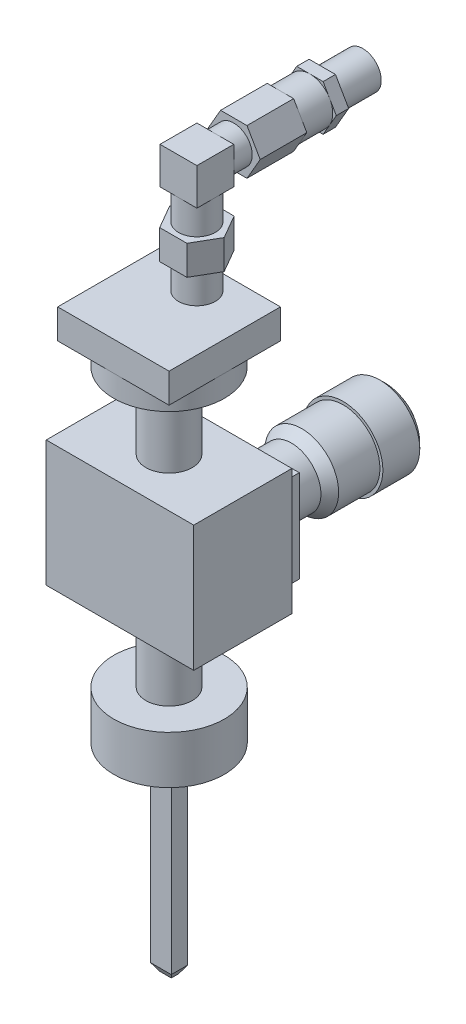
SolidWorks part; units mm, degrees
ref_plane "Front Plane" through (0, 0, 0) normal (0, 0, 1) x (1, 0, 0)
ref_plane "Top Plane" through (0, 0, 0) normal (0, 1, 0) x (1, 0, 0)
ref_plane "Right Plane" through (0, 0, 0) normal (1, 0, 0) x (0, 0, -1)
sketch "Sketch1" plane through (0, 0, 0) normal (0, 1, 0) x (1, 0, 0)
  line L1 (0, 0) -> (3.556, 0)
  line L2 (0, 0) -> (0, -2.794)
  line L3 (0, -2.794) -> (3.556, -2.794)
  line L4 (3.556, 0) -> (3.556, -2.794)
  line L5 (1.0922, -1.0795) -> (2.4638, -1.0795)
  line L6 (1.0922, -1.0795) -> (1.0922, -1.7145)
  line L7 (1.0922, -1.7145) -> (2.4638, -1.7145)
  line L8 (2.4638, -1.0795) -> (2.4638, -1.7145)
  point P9 (1.778, -1.0795)
  point P10 (1.778, 0)
  point P11 (2.4638, -1.397)
  point P12 (0, -1.397)
  dimension "D1" = 3.556
  dimension "D2" = 2.794
  dimension "D3" = 0.635
  dimension "D4" = 1.3716
extrude "Boss-Extrude1" add sketch "Sketch1" along normal blind 34.29 contours L4 L1 L2 L3 L5 L8 L7 L6 region at (1.778, 0, 0.0452)
sketch "Sketch2" plane through (0, 34.29, 0) normal (0, 1, 0) x (1, 0, 0)
  line L0 (1.0922, -1.0795) -> (2.4638, -1.0795) construction
  line L2 (1.0922, -1.0795) -> (1.0922, -1.7145) construction
  circle A0 centre (1.778, -1.397) radius 9.525
  point P5 (1.778, -1.0795)
  point P9 (1.0922, -1.397)
  dimension "D1" = 19.05
extrude "Boss-Extrude2" add sketch "Sketch2" along normal blind 8.255 contours A0
sketch "Sketch3" plane through (0, 42.545, 0) normal (0, 1, 0) x (1, 0, 0)
  circle A0 centre (1.778, -1.397) radius 4.0005
  circle A1 centre (1.778, -1.397) radius 9.525 construction
  dimension "D1" = 8.001
extrude "Boss-Extrude3" add sketch "Sketch3" along normal blind 13.081
sketch "Sketch4" plane through (0, 55.626, 0) normal (0, 1, 0) x (1, 0, 0)
  line L0 (-2.2225, -1.397) -> (5.7785, -1.397) construction
  line L1 (-10.922, 7.0549) -> (14.478, 7.0549)
  line L2 (-10.922, 7.0549) -> (-10.922, -9.8489)
  line L3 (-10.922, -9.8489) -> (14.478, -9.8488)
  line L4 (14.478, 7.0549) -> (14.478, -9.8488)
  circle A1 centre (1.778, -1.397) radius 4.0005 construction
  circle A2 centre (1.778, -1.397) radius 4.0005 construction
  point P11 (1.778, -1.397)
  point P12 (1.778, 7.0548)
  point P13 (-10.922, -1.397)
  dimension "D1" = 25.4
  dimension "D2" = 16.9037
extrude "Boss-Extrude4" add sketch "Sketch4" along normal blind 21.6662
sketch "Sketch5" plane through (0, 77.2922, 0) normal (0, 1, 0) x (1, 0, 0)
  circle A0 centre (1.778, -1.397) radius 4.0005
  circle A1 centre (1.778, -1.397) radius 4.0005 construction
extrude "Boss-Extrude5" add sketch "Sketch5" along normal blind 13.081
sketch "Sketch6" plane through (0, 90.3732, 0) normal (0, 1, 0) x (1, 0, 0)
  circle A0 centre (1.778, -1.397) radius 9.525
  dimension "D1" = 19.05
extrude "Boss-Extrude6" add sketch "Sketch6" along normal blind 3.81
sketch "Sketch7" plane through (0, 94.1832, 0) normal (0, 1, 0) x (1, 0, 0)
  line L0 (-7.747, -1.397) -> (11.303, -1.397) construction
  line L1 (-7.8105, 8.1915) -> (11.3665, 8.1915)
  line L2 (-7.8105, 8.1915) -> (-7.8105, -10.9855)
  line L3 (-7.8105, -10.9855) -> (11.3665, -10.9855)
  line L4 (11.3665, 8.1915) -> (11.3665, -10.9855)
  circle A0 centre (1.778, -1.397) radius 9.525 construction
  point P9 (1.778, 8.1915)
  point P10 (1.778, -1.397)
  point P11 (11.3665, -1.397)
  dimension "D1" = 19.177
  dimension "D2" = 19.177
extrude "Boss-Extrude7" add sketch "Sketch7" along normal blind 5.08
sketch "Sketch8" plane through (0, 99.2632, 0) normal (0, 1, 0) x (1, 0, 0)
  line L0 (11.3665, 8.1915) -> (-7.8105, 8.1915) construction
  line L1 (-7.8105, 8.1915) -> (-7.8105, -1.397) construction
  line L2 (-7.8105, 8.1915) -> (-7.8105, -10.9855) construction
  circle A0 centre (1.778, 3.3973) radius 3.175
  point P6 (1.778, 8.1915)
  point P10 (-7.8105, 3.3973)
  dimension "D1" = 6.35
extrude "Boss-Extrude8" add sketch "Sketch8" along normal blind 15.494
sketch "Sketch9" plane through (0, 114.7572, 0) normal (0, 1, 0) x (1, 0, 0)
  line L1 (-1.397, 6.5723) -> (4.953, 6.5723)
  line L2 (-1.397, 6.5723) -> (-1.397, 0.2223)
  line L3 (-1.397, 0.2223) -> (4.953, 0.2223)
  line L4 (4.953, 6.5723) -> (4.953, 0.2223)
  circle A0 centre (1.778, 3.3973) radius 3.175 construction
  circle A1 centre (1.778, 3.3973) radius 3.175 construction
extrude "Boss-Extrude9" add sketch "Sketch9" along normal blind 6.35
sketch "Sketch10" plane through (0, 0, -6.5723) normal (0, 0, -1) x (-1, 0, 0)
  line L0 (1.397, 121.1072) -> (1.397, 114.7572) construction
  line L1 (-4.953, 121.1072) -> (1.397, 121.1072) construction
  line L2 (-4.953, 121.1072) -> (-4.953, 114.7572) construction
  circle A0 centre (-1.778, 117.9322) radius 3.175
extrude "Boss-Extrude10" add sketch "Sketch10" along normal blind 3.175
sketch "Sketch11" plane through (0, 0, -9.7472) normal (0, 0, -1) x (-1, 0, 0)
  line L1 (0.495, 113.9952) -> (2.7681, 117.9322)
  line L2 (2.7681, 117.9322) -> (0.495, 121.8692)
  line L3 (0.495, 121.8692) -> (-4.051, 121.8692)
  line L4 (-4.051, 121.8692) -> (-6.3241, 117.9322)
  line L5 (-6.3241, 117.9322) -> (-4.051, 113.9952)
  line L6 (-4.051, 113.9952) -> (0.495, 113.9952)
  circle A1 centre (-1.778, 117.9322) radius 3.175 construction
  circle A2 centre (-1.778, 117.9322) radius 3.937 construction
  dimension "D1" = 7.874
extrude "Boss-Extrude11" add sketch "Sketch11" along normal blind 15.24
sketch "Sketch12" plane through (0, 0, -24.9872) normal (0, 0, -1) x (-1, 0, 0)
  circle A0 centre (-1.778, 117.9322) radius 3.175
  circle A2 centre (-1.778, 117.9322) radius 3.937 construction
  dimension "D1" = 6.35
extrude "Boss-Extrude12" add sketch "Sketch12" along normal blind 6.985
sketch "Sketch13" plane through (0, 0, -7.0549) normal (0, 0, -1) x (-1, 0, 0)
  line L0 (-14.478, 77.2922) -> (10.922, 77.2922) construction
  line L1 (-13.208, 74.7522) -> (2.6924, 74.7522)
  line L2 (-13.208, 74.7522) -> (-13.208, 58.8772)
  line L3 (-13.208, 58.8772) -> (2.6924, 58.8772)
  line L4 (2.6924, 74.7522) -> (2.6924, 58.8772)
  line L5 (-14.478, 77.2922) -> (-14.478, 55.626) construction
  dimension "D1" = 15.9004
  dimension "D2" = 15.875
  dimension "D3" = 2.54
  dimension "D4" = 1.27
extrude "Boss-Extrude13" add sketch "Sketch13" along normal blind 2.54
sketch "Sketch15" plane through (0, 0, -9.5949) normal (0, 0, -1) x (-1, 0, 0)
  line L0 (-5.2578, 74.7522) -> (-5.2578, 58.8772) construction
  line L1 (2.6924, 74.7522) -> (-13.208, 74.7522) construction
  line L2 (-13.208, 58.8772) -> (2.6924, 58.8772) construction
ref_plane "Plane1" through (5.2578, 0, 0) normal (1, 0, 0) x (0, 0, -1)
sketch "Sketch16" plane through (5.2578, 0, 0) normal (1, 0, 0) x (0, 0, -1)
  line L0 (9.5949, 66.8147) -> (36.0527, 66.8147) construction
  line L1 (9.5949, 74.7522) -> (9.5949, 58.8772) construction
  line L2 (9.5949, 66.8147) -> (9.5949, 71.8947)
  line L3 (9.5949, 71.8947) -> (16.1989, 71.8947)
  line L4 (16.1989, 71.8947) -> (17.9768, 73.1647)
  line L5 (17.9768, 73.1647) -> (25.0889, 73.1647)
  line L6 (25.0889, 73.1647) -> (25.0889, 73.6727)
  line L7 (25.0889, 73.6727) -> (31.4388, 73.6727)
  line L8 (34.7408, 66.8147) -> (9.5949, 66.8147)
  line L9 (34.7408, 66.8147) -> (34.7408, 68.0847)
  line L10 (34.7408, 68.0847) -> (34.4868, 68.0847)
  arc A0 (31.4388, 73.6727) -> (34.4868, 68.0847) centre (25.5122, 66.8147) cw
  point P4 (9.5949, 66.8147)
  dimension "D9" = 0.254
  dimension "D1" = 5.08
  dimension "D2" = 6.604
  dimension "D3" = 6.35
  dimension "D4" = 8.89
  dimension "D5" = 7.112
  dimension "D6" = 6.858
  dimension "D7" = 6.35
  dimension "D8" = 25.146
  dimension "D10" = 1.27
revolve "Revolve1" add sketch "Sketch16" angle 360 about L0
ref_plane "Plane2" through (0, 107.0102, 0) normal (0, 1, 0) x (1, 0, 0)
sketch "Sketch17" plane through (0, 107.0102, 0) normal (0, 1, 0) x (1, 0, 0)
  line L0 (4.953, 6.5723) -> (1.778, 6.5723) construction
  line L1 (6.4707, 3.3973) -> (4.1244, 7.4612)
  line L2 (4.1244, 7.4612) -> (-0.5684, 7.4612)
  line L3 (-0.5684, 7.4612) -> (-2.9147, 3.3972)
  line L4 (-2.9147, 3.3972) -> (-0.5684, -0.6668)
  line L5 (-0.5684, -0.6668) -> (4.1244, -0.6667)
  line L6 (4.1244, -0.6667) -> (6.4707, 3.3973)
  circle A0 centre (1.778, 3.3973) radius 4.064 construction
  circle A2 centre (1.778, 3.3973) radius 3.175 construction
  dimension "D1" = 8.128
extrude "Boss-Extrude15" add sketch "Sketch17" along normal mid plane 5.08
sketch "Sketch20" plane through (0, 0, 0) normal (-1, 0, 0) x (0, 0, 1)
  line L0 (0, 0) -> (0.762, 0)
  line L1 (0, 0) -> (2.794, 0) construction
  line L2 (0.762, 0) -> (0, 1.27)
  line L3 (0, 34.29) -> (0, 0) construction
  line L4 (0, 1.27) -> (0, 0)
  line L5 (2.794, 0) -> (2.794, 1.27)
  line L6 (2.794, 34.29) -> (2.794, 0) construction
  line L7 (2.794, 1.27) -> (2.032, 0)
  line L8 (2.032, 0) -> (2.794, 0)
  dimension "D1" = 1.27
  dimension "D2" = 1.27
  dimension "D3" = 0.762
  dimension "D4" = 0.762
extrude "Cut-Extrude1" cut sketch "Sketch20" against normal blind 15
sketch "Sketch21" plane through (0, 0, 0) normal (0, 0, -1) x (-1, 0, 0)
  line L0 (-3.556, 1.27) -> (-3.556, 0)
  line L1 (-3.556, 0) -> (-2.794, 0)
  line L2 (0, 0) -> (-3.556, 0) construction
  line L3 (-2.794, 0) -> (-3.556, 1.27)
  line L4 (0, 1.27) -> (-0.762, 0)
  line L5 (-0.762, 0) -> (0, 0)
  line L6 (0, 0) -> (0, 1.27)
  dimension "D1" = 0.762
extrude "Cut-Extrude2" cut sketch "Sketch21" against normal blind 15
fillet "Fillet1" radius 1.27 4 edges at (3.556, 34.29, 1.397) (1.778, 34.29, 2.794) (0, 34.29, 1.397) (1.778, 34.29, 0)
sketch "Sketch22" plane through (0, 0, -31.9722) normal (0, 0, -1) x (-1, 0, 0)
  circle A0 centre (-1.778, 117.9322) radius 2.54
  circle A1 centre (-1.778, 117.9322) radius 3.175 construction
  circle A2 centre (-1.778, 117.9322) radius 0.127
  dimension "D1" = 5.08
  dimension "D2" = 0.254
extrude "Cut-Extrude3" cut sketch "Sketch22" against normal blind 3.81 contours A0 A2 region at (4.2462, 117.9322, -31.9722)
extrude "Cut-Extrude4" cut sketch "Sketch22<3>" against normal blind 12.7 contours A2 region at (1.778, 117.9322, -31.9722)
sketch "Sketch22<3>" plane through (0, 0, -31.9722) normal (0, 0, -1) x (-1, 0, 0) same geometry as "Sketch22"
ref_plane "Plane4" through (0, 0, -17.78) normal (0, 0, 1) x (1, 0, 0)
sketch "Sketch25" plane through (0, 0, -17.78) normal (0, 0, 1) x (1, 0, 0)
  line L1 (-2.7681, 117.9322) -> (-0.495, 113.9952)
  line L2 (-0.495, 113.9952) -> (4.051, 113.9952)
  line L3 (4.051, 113.9952) -> (6.3241, 117.9322)
  line L4 (6.3241, 117.9322) -> (4.051, 121.8692)
  line L5 (4.051, 121.8692) -> (-0.495, 121.8692)
  line L6 (-0.495, 121.8692) -> (-2.7681, 117.9322)
  circle A0 centre (1.778, 117.9322) radius 3.937
  circle A1 centre (1.778, 117.9322) radius 3.937 construction
  circle A2 centre (1.778, 117.9322) radius 3.937 construction
extrude "Cut-Extrude7" cut sketch "Sketch25" against normal blind 5.08 contours A0 L5 L6 | A0 L4 L5 | A0 L1 L2 | A0 L6 L1 | A0 L2 L3 | A0 L3 L4 region at (-2.2911, 117.9322, -17.78) region at (-0.2566, 114.4082, -17.78) region at (-0.2566, 121.4562, -17.78) region at (3.8126, 114.4082, -17.78) region at (3.8126, 121.4562, -17.78) region at (5.8471, 117.9322, -17.78)
